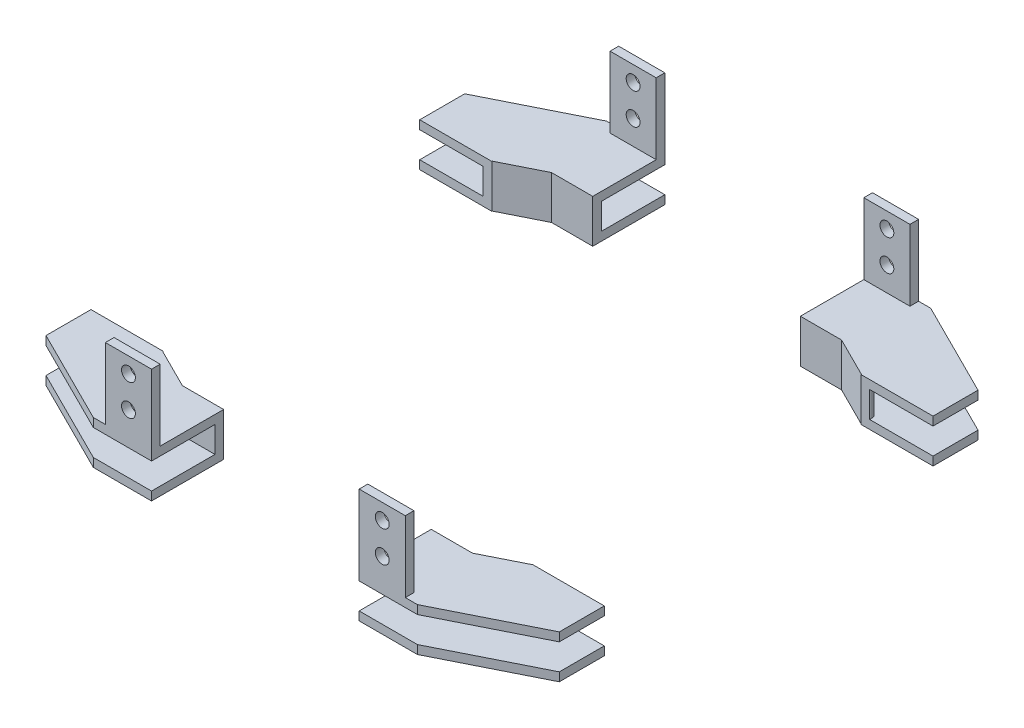
SolidWorks part; units mm, degrees
note: The reader was unsure of these and kept them because the rebuilt part matched: shared geometry of "Sketch5<2>".
ref_plane "Front Plane" through (0, 0, 0) normal (0, 0, 1) x (1, 0, 0)
ref_plane "Top Plane" through (0, 0, 0) normal (0, 1, 0) x (1, 0, 0)
ref_plane "Right Plane" through (0, 0, 0) normal (1, 0, 0) x (0, 0, -1)
sketch "Sketch1" plane through (0, 0, 0) normal (0, 1, 0) x (1, 0, 0)
  line L5 (-33.5, 0) -> (0, 0) construction
  line L6 (-25.5, -33.5) -> (25.5, -33.5)
  line L10 (-33.5, -29.5) -> (-33.5, 29.5)
  line L11 (-25.5, 33.5) -> (25.5, 33.5)
  line L12 (33.5, -29.5) -> (33.5, 29.5)
  line L13 (0, 0) -> (0, 33.5) construction
  line L14 (25.5, -33.5) -> (33.5, -29.5)
  line L15 (25.5, 33.5) -> (33.5, 29.5)
  line L16 (-25.5, -33.5) -> (-33.5, -29.5)
  line L17 (-25.5, 33.5) -> (-33.5, 29.5)
  point P0 (0, 0)
  point P4 (33.5, -33.5)
  dimension "D3" = 4
  dimension "D2" = 8
  dimension "D4" = 67
extrude "Boss-Extrude1" add sketch "Sketch1" along normal mid plane 4.5
sketch "Sketch2" plane through (0, 2.25, 0) normal (0, 1, 0) x (1, 0, 0)
  line L16 (28.0967, -44.5) -> (44.5, -36.2984)
  line L17 (44.5, -36.2984) -> (44.5, 36.2984)
  line L18 (44.5, 36.2984) -> (28.0967, 44.5)
  line L19 (28.0967, 44.5) -> (-28.0967, 44.5)
  line L20 (-28.0967, 44.5) -> (-44.5, 36.2984)
  line L21 (-44.5, 36.2984) -> (-44.5, -36.2984)
  line L22 (-44.5, -36.2984) -> (-28.0967, -44.5)
  line L23 (-28.0967, -44.5) -> (28.0967, -44.5)
  line L24 (28.0967, -44.5) -> (44.5, -36.2984)
  line L25 (44.5, -36.2984) -> (44.5, 36.2984)
  line L26 (44.5, 36.2984) -> (28.0967, 44.5)
  line L27 (28.0967, 44.5) -> (-28.0967, 44.5)
  line L28 (-28.0967, 44.5) -> (-44.5, 36.2984)
  line L29 (-44.5, 36.2984) -> (-44.5, -36.2984)
  line L30 (-44.5, -36.2984) -> (-28.0967, -44.5)
  line L31 (-28.0967, -44.5) -> (28.0967, -44.5)
  dimension "D1" = 11
extrude "Boss-Extrude2" add sketch "Sketch2" along normal blind 1.5
mirror "Mirror1" about plane through (0, 0, 0) normal (0, 1, 0) of "Boss-Extrude2"
sketch "Sketch3" plane through (0, 0, 0) normal (0, 1, 0) x (1, 0, 0)
  line L16 (-25.1459, -32) -> (25.1459, -32)
  line L17 (25.1459, -32) -> (32, -28.5729)
  line L18 (32, -28.5729) -> (32, 28.5729)
  line L19 (32, 28.5729) -> (25.1459, 32)
  line L20 (25.1459, 32) -> (-25.1459, 32)
  line L21 (-25.1459, 32) -> (-32, 28.5729)
  line L22 (-32, 28.5729) -> (-32, -28.5729)
  line L23 (-32, -28.5729) -> (-25.1459, -32)
  line L24 (-25.1459, -32) -> (25.1459, -32)
  line L25 (25.1459, -32) -> (32, -28.5729)
  line L26 (32, -28.5729) -> (32, 28.5729)
  line L27 (32, 28.5729) -> (25.1459, 32)
  line L28 (25.1459, 32) -> (-25.1459, 32)
  line L29 (-25.1459, 32) -> (-32, 28.5729)
  line L30 (-32, 28.5729) -> (-32, -28.5729)
  line L31 (-32, -28.5729) -> (-25.1459, -32)
  dimension "D1" = 12.5
extrude "Cut-Extrude1" cut sketch "Sketch3" against normal through all both and the other way through all
sketch "Sketch5" plane through (0, 0, 0) normal (0, 0, 1) x (1, 0, 0)
  line L0 (0, 0) -> (0, 28.4264) construction
  line L1 (-28.0967, 3.75) -> (28.0967, 3.75) construction
  line L2 (-26, 3.75) -> (-18, 3.75)
  line L3 (-26, 3.75) -> (-26, 16.05)
  line L4 (-26, 16.05) -> (-18, 16.05)
  line L5 (-18, 3.75) -> (-18, 16.05)
  line L6 (-22, 16.05) -> (-22, 9.7096) construction
  line L7 (18, 3.75) -> (18, 16.05)
  line L8 (26, 16.05) -> (18, 16.05)
  line L9 (26, 3.75) -> (26, 16.05)
  line L10 (26, 3.75) -> (18, 3.75)
  dimension "D1" = 22
  dimension "D3" = 12.3
  dimension "D2" = 8
extrude "Boss-Extrude3" add sketch "Sketch5" against normal blind 1.5 from surface at 44.5 starting at face at (0, 3, 44.5)
extrude "Boss-Extrude4" add sketch "Sketch5<2>" along normal blind 1.5 from surface at -44.5 starting at face at (0, 3, -44.5)
sketch "Sketch5<2>" plane through (0, 0, 0) normal (0, 0, 1) x (1, 0, 0) same geometry as "Sketch5"
sketch "Sketch6" plane through (0, 0, 0) normal (0, 0, 1) x (1, 0, 0)
  line L0 (-22, 16.05) -> (-22, 13.35) construction
  line L1 (-18, 16.05) -> (-26, 16.05) construction
  line L2 (0, 0) -> (0, 25.5714) construction
  line L3 (22, 13.35) -> (22, 7.95) construction
  circle A0 centre (-22, 13.35) radius 1.2
  circle A1 centre (22, 13.35) radius 1.2
  circle A2 centre (22, 7.95) radius 1.2
  circle A3 centre (-22, 7.95) radius 1.2
  dimension "D1" = 2.4
  dimension "D2" = 2.7
  dimension "D3" = 5.4
extrude "Cut-Extrude3" cut sketch "Sketch6" against normal through all both and the other way through all
sketch "Sketch7" plane through (0, 0, 0) normal (0, 1, 0) x (1, 0, 0)
  line L0 (44.5, -36.2984) -> (44.5, 36.2984) construction
  line L1 (-44.5, -28.5) -> (44.5, -28.5)
  line L2 (-44.5, -28.5) -> (-44.5, 28.5)
  line L3 (-44.5, 28.5) -> (44.5, 28.5)
  line L4 (44.5, -28.5) -> (44.5, 28.5)
  line L5 (-44.5, -28.5) -> (44.5, 28.5) construction
  line L6 (-44.5, 28.5) -> (44.5, -28.5) construction
  point P0 (0, 0)
  dimension "D1" = 57
extrude "Cut-Extrude6" cut sketch "Sketch7" against normal through all both and the other way through all
sketch "Sketch8" plane through (0, 0, 0) normal (0, 1, 0) x (1, 0, 0)
  line L1 (-18, -44.5) -> (18, -44.5)
  line L2 (-18, -44.5) -> (-18, 44.5)
  line L3 (-18, 44.5) -> (18, 44.5)
  line L4 (18, -44.5) -> (18, 44.5)
  line L5 (-18, -44.5) -> (18, 44.5) construction
  line L6 (-18, 44.5) -> (18, -44.5) construction
  point P0 (0, 0)
extrude "Cut-Extrude7" cut sketch "Sketch8" against normal through all both and the other way through all
fillet "Fillet1" radius 1 2 edges at (33.5, 0, 29.5) (25.5, 0, 33.5)
fillet "Fillet2" radius 1 2 edges at (33.5, 0, -29.5) (25.5, 0, -33.5)
fillet "Fillet3" radius 1 2 edges at (-33.5, 0, -29.5) (-25.5, 0, -33.5)
fillet "Fillet4" radius 1 2 edges at (-33.5, 0, 29.5) (-25.5, 0, 33.5)
other "Save Bodies1"
